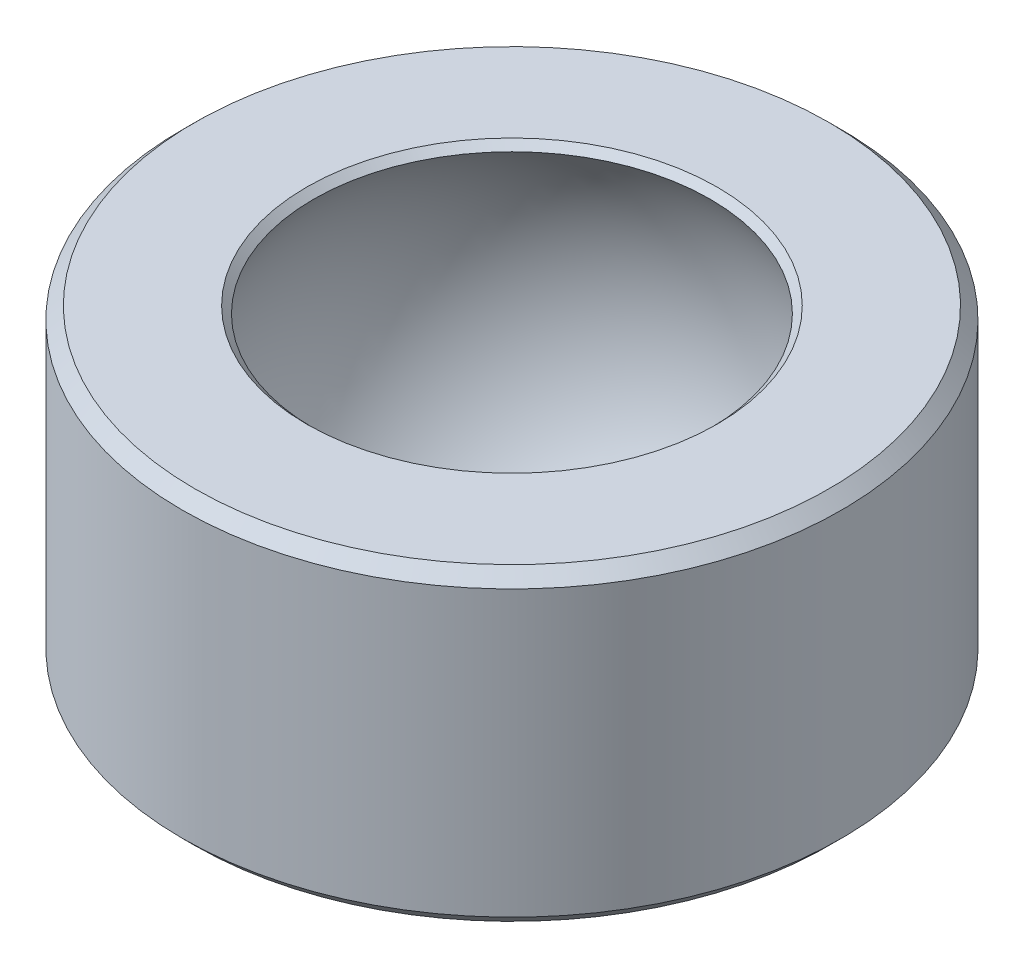
SolidWorks part; units mm, degrees
ref_plane "Front Plane" through (0, 0, 0) normal (0, 0, 1) x (1, 0, 0)
ref_plane "Top Plane" through (0, 0, 0) normal (0, 1, 0) x (1, 0, 0)
ref_plane "Right Plane" through (0, 0, 0) normal (1, 0, 0) x (0, 0, -1)
sketch "Sketch1" plane through (0, 0, 0) normal (0, 1, 0) x (1, 0, 0)
  circle A0 centre (0, 0) radius 2
  circle A1 centre (0, 0) radius 3 construction
  circle A2 centre (0, 0) radius 4
  dimension "D1" = 6
  dimension "D2" = 8
  dimension "D3" = 4
extrude "Boss-Extrude1" add sketch "Sketch1" along normal blind 1.875 and the other way blind 1.875
sketch "Sketch2" plane through (0, 0, 0) normal (0, 1, 0) x (1, 0, 0)
  line L0 (0, 3) -> (0, -3)
  circle A0 centre (0, 0) radius 3 construction
  arc A1 (0, 3) -> (0, -3) centre (0, 0) ccw
revolve "Revolve1" add sketch "Sketch2" angle 360 about L0
combine bodies "Combine1" operation type subtract main body 101 bodies to subtract 102
chamfer "Chamfer1" distance 0.15 angle 45 4 edges at (0, 1.875, 4) (0, -1.875, 4) (0, -1.875, 2.3419) (0, 1.875, 2.3419) first distance on face at (0, -1.875, 4) first distance on face at (0, -1.875, 2.3419) first distance on face at (0, 1.875, 2.3419)
